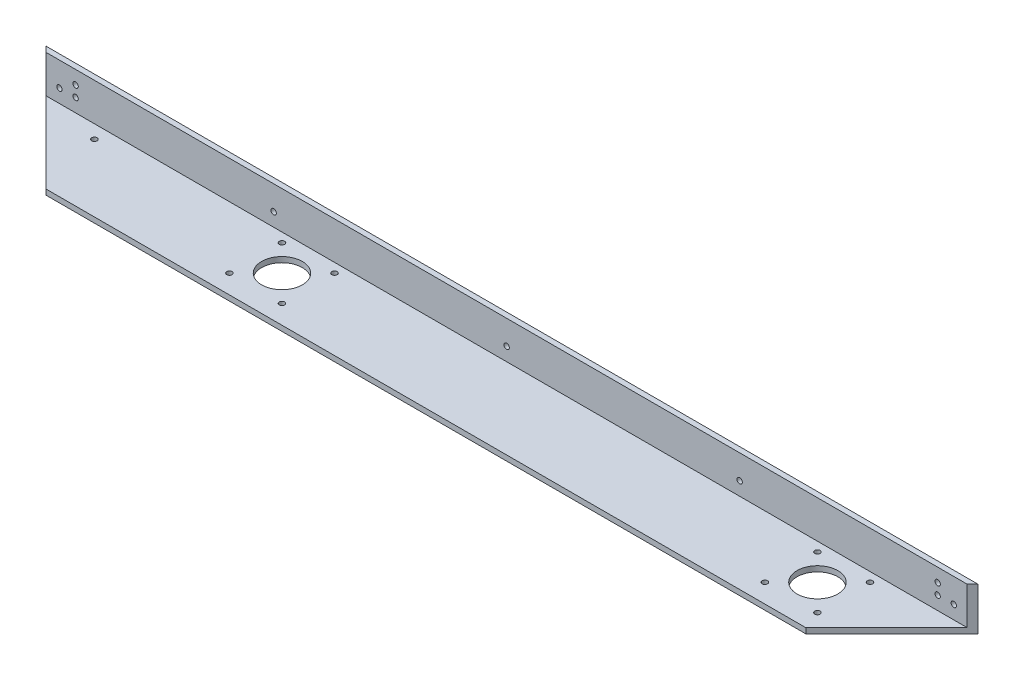
SolidWorks part; units mm, degrees
ref_plane "Front Plane" through (0, 0, 0) normal (0, 0, 1) x (1, 0, 0)
ref_plane "Top Plane" through (0, 0, 0) normal (0, 1, 0) x (1, 0, 0)
ref_plane "Right Plane" through (0, 0, 0) normal (1, 0, 0) x (0, 0, -1)
sketch "Sketch1" plane through (0, 0, 0) normal (1, 0, 0) x (0, 0, -1)
  line L0 (0, 0) -> (-50.8, 0)
  line L1 (-50.8, 0) -> (-50.8, 3.175)
  line L2 (-50.8, 3.175) -> (-3.175, 3.175)
  line L3 (-3.175, 3.175) -> (-3.175, 25.4)
  line L4 (-3.175, 25.4) -> (0, 25.4)
  line L5 (0, 25.4) -> (0, 0)
  dimension "LHeight" = 25.4
  dimension "LWidth" = 50.8
  dimension "LMaterialThickness" = 3.175
  dimension "D1" = 47.625
  dimension "D2" = 22.225
  dimension "D3" = 3.175
extrude "Boss-Extrude1" add sketch "Sketch1" along normal blind 550
chamfer "Chamfer7" distance 50.8 angle 45 1 edges at (0, 1.5875, 50.8)
chamfer "Chamfer8" distance 50.8 angle 45 1 edges at (550, 1.5875, 50.8)
sketch "BotthomHoles-Sketch2" plane through (0, 3.175, 0) normal (0, 1, 0) x (1, 0, 0)
  line L0 (546.825, -3.175) -> (3.175, -3.175) construction
  line L1 (550, 0) -> (0, 0) construction
  circle A0 centre (479.425, -24.175) radius 12
  circle A2 centre (463.925, -8.675) radius 1.5875
  circle A3 centre (494.925, -8.675) radius 1.5875
  circle A6 centre (463.925, -39.675) radius 1.5875
  circle A7 centre (494.925, -39.675) radius 1.5875
  circle A8 centre (39.6875, -11.1125) radius 1.5875
  circle A10 centre (178.925, -39.675) radius 1.5875
  circle A11 centre (147.925, -39.675) radius 1.5875
  circle A12 centre (178.925, -8.675) radius 1.5875
  circle A13 centre (147.925, -8.675) radius 1.5875
  circle A14 centre (163.425, -24.175) radius 12
  dimension "D9" = 3.175
  dimension "D10" = 24
  dimension "D13" = 3.175
  dimension "D2" = 8.675
  dimension "D5" = 15.5
  dimension "D6" = 31
  dimension "D7" = 15.5
  dimension "D8" = 31
  dimension "D11" = 21
  dimension "D3" = 70.575
  dimension "D4" = 11.1125
  dimension "D12" = 39.6875
  dimension "D15" = 31
  dimension "D16" = 15.5
  dimension "D17" = 316
extrude "BottomHoles-Cut-Extrude1" cut sketch "BotthomHoles-Sketch2" against normal through all
sketch "RightSideHoles-Sketch3" plane through (0, 0, 0) normal (0, 0, -1) x (-1, 0, 0)
  line L0 (-550, 0) -> (-550, 25.4) construction
  line L1 (0, 0) -> (0, 25.4) construction
  line L2 (-550, 25.4) -> (0, 25.4) construction
  circle A1 centre (-529.3625, 17.4625) radius 1.5875
  circle A2 centre (-538.8875, 11.1125) radius 1.5875
  circle A3 centre (-529.3625, 11.1125) radius 1.5875
  circle A4 centre (-11.1125, 11.1125) radius 1.5875
  circle A5 centre (-20.6375, 11.1125) radius 1.5875
  circle A6 centre (-20.6375, 17.4625) radius 1.5875
  circle A8 centre (-412.5, 11.1125) radius 1.5875
  circle A9 centre (-275, 11.1125) radius 1.5875
  circle A10 centre (-137.5, 11.1125) radius 1.5875
  dimension "D4" = 11.1125
  dimension "D7" = 3.175
  dimension "D2" = 20.6375
  dimension "D6" = 20.6375
  dimension "D8" = 137.5
  dimension "D9" = 137.5
  dimension "D10" = 137.5
  dimension "D5" = 11.1125
  dimension "D11" = 11.1125
  dimension "D3" = 7.9375
extrude "RightSideHoles-Cut-Extrude2" cut sketch "RightSideHoles-Sketch3" against normal through all
equation "\"LowerRailWidth\"= 2.00in"
equation "\"LowerRailHeight\"= 1.00in"
equation "\"RailThickness\"= .125in'Spec"
equation "\"SideRailHoleY1FromEdge\"= \"HoleOffsetFromEdge\""
equation "\"SideRailHoleX1FromSide\"= \"HoleOffsetFromSide\""
equation "\"StepperHoleDiameter\"= 24mm"
equation "\"StepperMountingHoleDiameter\"= 3.175mm"
equation "\"SideRailLength\"= 550mm"
equation "\"StepperMountingHoleDistance\"= 31mm'Spec"
equation "\"VSWidth\"= 1.25in'Spec"
equation "\"StepperMountingHoleOffsetFromLeftOrRightSide\"= \"StepperMountingHoleOffsetFromItsSide\" + \"RailThickness\""
equation "\"HoleOffsetFromEdge\"= \"RailThickness\" * 2.5"
equation "\"HoleOffsetFromSide\"= \"RailThickness\" * 3.5"
equation "\"StepperMountingHoleOffsetFromItsSide\"= 5.5mm'Spec"
equation "\"SideRailHoleX2FromSide\"= \"VSWidth\" - \"HoleOffsetFromEdge\" - \"RailThickness\"'Equals 20.6375"
equation "\"FasteningHoleDiameter\"= .125in"
equation "\"SideRailHoleY2FromSide\"= \"HoleOffsetFromSide\""
equation "\"LHeight@Sketch1\"=\"LowerRailHeight\""
equation "\"LWidth@Sketch1\"=\"LowerRailWidth\""
equation "\"D1@Chamfer7\"=\"LowerRailWidth\""
equation "\"D1@Chamfer8\"=\"LowerRailWidth\""
equation "\"D2@BotthomHoles-Sketch2\" = \"StepperMountingHoleOffsetFromLeftOrRightSide\""
equation "\"D5@BotthomHoles-Sketch2\" = \"StepperMountingHoleDistance\" / 2"
equation "\"D6@BotthomHoles-Sketch2\" = \"StepperMountingHoleDistance\""
equation "\"D7@BotthomHoles-Sketch2\" = \"StepperMountingHoleDistance\" / 2"
equation "\"D8@BotthomHoles-Sketch2\" = \"StepperMountingHoleDistance\""
equation "\"D9@BotthomHoles-Sketch2\" = \"StepperMountingHoleDiameter\""
equation "\"D10@BotthomHoles-Sketch2\" = \"StepperHoleDiameter\""
equation "\"D2@RightSideHoles-Sketch3\" = \"SideRailHoleX2FromSide\""
equation "\"D4@RightSideHoles-Sketch3\" = \"SideRailHoleY2FromSide\""
equation "\"D7@RightSideHoles-Sketch3\" = \"FasteningHoleDiameter\""
equation "\"D1@Boss-Extrude1\"=\"SideRailLength\""
equation "\"D6@RightSideHoles-Sketch3\"=\"SideRailHoleX2FromSide\""
equation "\"BedThirdSize\"= 70mm"
equation "\"BedInnerSquareWidth\"= \"BedThirdSize\" * 3'Equals 210"
equation "\"BedInnerSquareLength\"= \"BedInnerSquareWidth\""
equation "\"BedLWidth\" = \"BedThirdSize\"'Equals 70"
equation "\"BedLength\" = \"BedInnerSquareLength\" + \"BedLWidth\" * 2 + \"BedIncreasedByLength\"'Equals 350"
equation "\"DistanceBetweenFrontToBackStepperHoles\"= \"BedLength\" - \"DistanceFromBedFrontToFirstLeftStepperHole\"'Equals 316"
equation "\"D3@BotthomHoles-Sketch2\"=\"DistanceFromFrontSideToFirstLeftStepperHole\""
equation "\"DistanceFromBedFrontToFirstLeftStepperHole\"= \"LeadScrewNutPadSize\" + 10mm'Equals 34"
equation "\"DistanceFromFrontSideToBedFront\"= \"RailThickness\" + \"BeltTensionerDepth\" + 10mm'Equals 36.575"
equation "\"20TGT2PulleyDiameter\"= 17.9mm'Spec"
equation "\"BeltTensionerBackWallThickness\"= 4mm"
equation "\"BeltTensionerSpaceBetweenPulleyAndWall\"= 1.5mm"
equation "\"BeltTensionerInnerDepth\"= \"20TGT2PulleyDiameter\" + \"BeltTensionerSpaceBetweenPulleyAndWall\""
equation "\"BeltTensionerDepth\"= \"BeltTensionerBackWallThickness\" + \"BeltTensionerInnerDepth\"'Equals 23.4"
equation "\"BedIncreasedByLength\"= 0mm"
equation "\"LowerCornerBlockWidth\"= \"LowerRailWidth\" - \"RailThickness\" * 2'Room for left front stepper"
equation "\"D4@BotthomHoles-Sketch2\"=\"LowerCornerBlockY1FromSide\""
equation "\"D12@BotthomHoles-Sketch2\"=\"CornerEnclosureOffset\""
equation "\"D13@BotthomHoles-Sketch2\"=\"FasteningHoleDiameter\""
equation "\"CornerEnclosureOffset\"= \"LowerCornerBlockWidth\" - \"HoleOffsetFromEdge\" + \"RailThickness\""
equation "\"LowerCornerBlockY1FromSide\"= \"HoleOffsetFromSide\""
equation "\"D15@BotthomHoles-Sketch2\"=\"StepperMountingHoleDistance\""
equation "\"D16@BotthomHoles-Sketch2\"=\"StepperMountingHoleDistance\"/2"
equation "\"D17@BotthomHoles-Sketch2\"=\"DistanceBetweenFrontToBackStepperHoles\""
equation "\"DistanceFromFrontSideToFirstLeftStepperHole\"= \"DistanceFromFrontSideToBedFront\" + \"DistanceFromBedFrontToFirstLeftStepperHole\"'Equals 70.575"
equation "\"LeadScrewNutMountingHoleFlangeDiameter\"= 22mm'Spec"
equation "\"LeadScrewNutPadSize\"= \"LeadScrewNutMountingHoleFlangeDiameter\" + 2mm'Equals 24"
equation "\"LeftOrRightEnclosureOffsets\"= \"SideRailLength\" / 4"
equation "\"D8@RightSideHoles-Sketch3\"=\"LeftOrRightEnclosureOffsets\""
equation "\"D9@RightSideHoles-Sketch3\"=\"LeftOrRightEnclosureOffsets\""
equation "\"D10@RightSideHoles-Sketch3\"=\"LeftOrRightEnclosureOffsets\""
equation "\"D5@RightSideHoles-Sketch3\"=\"SideRailHoleX1FromSide\""
equation "\"D11@RightSideHoles-Sketch3\"=\"SideRailHoleX1FromSide\""
equation "\"D3@RightSideHoles-Sketch3\"=\"SideRailHoleY1FromEdge\""
